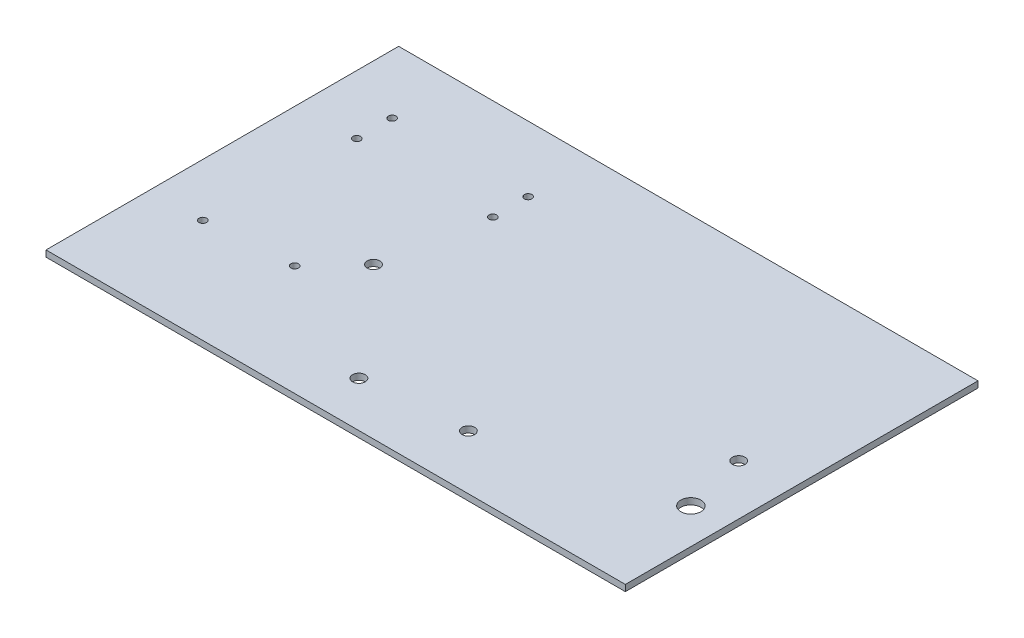
SolidWorks part; units mm, degrees
ref_plane "Front Plane" through (0, 0, 0) normal (0, 0, 1) x (1, 0, 0)
ref_plane "Top Plane" through (0, 0, 0) normal (0, 1, 0) x (1, 0, 0)
ref_plane "Right Plane" through (0, 0, 0) normal (1, 0, 0) x (0, 0, -1)
sketch "Sketch1" plane through (0, 0, 0) normal (0, 1, 0) x (1, 0, 0)
  line L1 (-158.75, 88.9) -> (158.75, 88.9)
  line L2 (-158.75, 88.9) -> (-158.75, -88.9)
  line L3 (-158.75, -88.9) -> (158.75, -88.9)
  line L4 (158.75, 88.9) -> (158.75, -88.9)
  line L5 (-158.75, 88.9) -> (158.75, -88.9) construction
  line L6 (-158.75, -88.9) -> (158.75, 88.9) construction
  circle A0 centre (-69.85, -12.7) radius 3.175
  circle A1 centre (107.95, -6.35) radius 3.175
  circle A4 centre (-129.032, 55.88) radius 1.905
  circle A5 centre (-60.452, 55.88) radius 1.905
  circle A7 centre (-129.032, 38.1) radius 1.905
  circle A8 centre (-60.452, 38.1) radius 1.905
  point P0 (0, 0)
  dimension "D3" = 6.35
  dimension "D4" = 6.35
  dimension "D14" = 3.81
  dimension "D17" = 17.78
  dimension "D1" = 317.5
  dimension "D2" = 177.8
  dimension "D5" = 88.9
  dimension "D6" = 266.7
  dimension "D7" = 95.25
  dimension "D8" = 76.2
  dimension "D13" = 29.718
  dimension "D15" = 68.58
  dimension "D16" = 127
extrude "Boss-Extrude1" add sketch "Sketch1" along normal blind 3.175
sketch "Sketch2" plane through (0, 3.175, 0) normal (0, 1, 0) x (1, 0, 0)
  line L0 (-158.75, 88.9) -> (-158.75, -88.9) construction
  line L1 (-158.75, -88.9) -> (158.75, -88.9) construction
  circle A0 centre (-89.0817, -33.177) radius 1.905
  circle A1 centre (-132.1376, -36.4483) radius 1.905
  dimension "D1" = 3.81
  dimension "D2" = 69.6683
  dimension "D3" = 52.4517
  dimension "D4" = 55.723
  dimension "D5" = 43.18
extrude "Cut-Extrude1" cut sketch "Sketch2" against normal through all
sketch "Sketch3" plane through (0, 0, 0) normal (0, -1, 0) x (-1, 0, 0)
  line L0 (158.75, -88.9) -> (-158.75, -88.9) construction
  line L1 (158.75, 88.9) -> (158.75, -88.9) construction
  circle A0 centre (23.8295, -66.04) radius 3.175
  circle A1 centre (-26.7643, -61.468) radius 3.175
  dimension "D1" = 6.35
  dimension "D2" = 4.572
  dimension "D3" = 22.86
  dimension "D4" = 185.5143
  dimension "D5" = 50.8
extrude "Cut-Extrude2" cut sketch "Sketch3" against normal through all
sketch "Sketch4" plane through (0, 3.175, 0) normal (0, 1, 0) x (1, 0, 0)
  line L0 (-158.75, -88.9) -> (158.75, -88.9) construction
  line L1 (158.75, 88.9) -> (133.35, 88.9)
  line L2 (158.75, 88.9) -> (158.75, -88.9)
  line L3 (158.75, -88.9) -> (133.35, -88.9)
  line L4 (133.35, 88.9) -> (133.35, -88.9)
  dimension "D1" = 25.4
extrude "Cut-Extrude3" cut sketch "Sketch4" against normal through all
sketch "Sketch5" plane through (0, 3.175, 0) normal (0, 1, 0) x (1, 0, 0)
  line L0 (133.35, 88.9) -> (-158.75, 88.9) construction
  line L1 (133.35, 88.9) -> (133.35, -88.9) construction
  circle A0 centre (115.57, -38.1) radius 5.08
  dimension "D3" = 10.16
  dimension "D1" = 127
  dimension "D2" = 17.78
extrude "Cut-Extrude4" cut sketch "Sketch5" against normal through all
